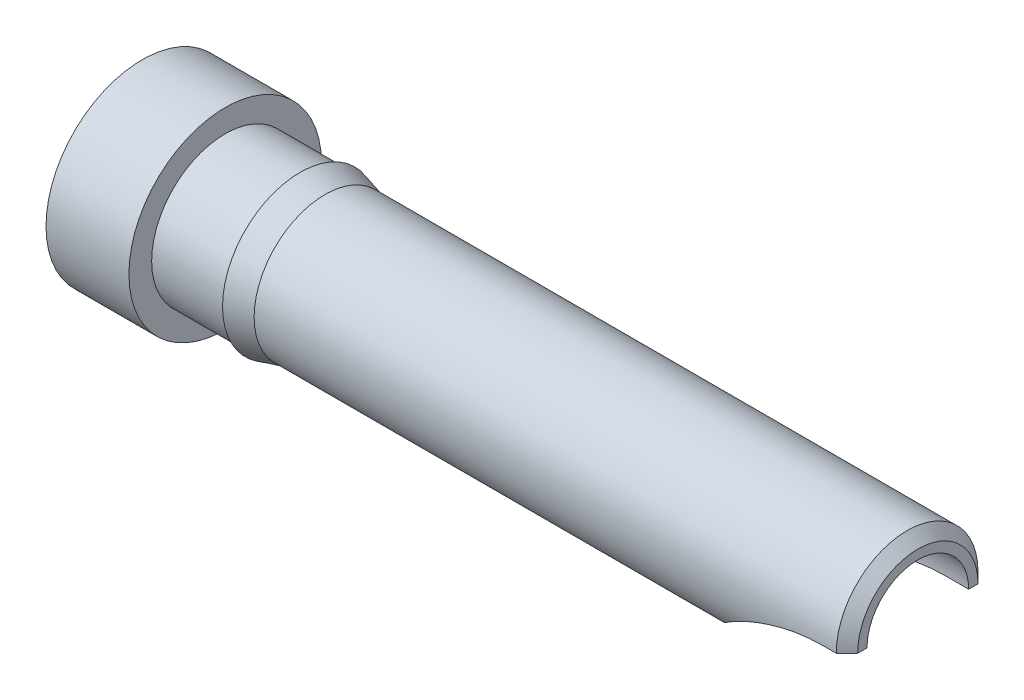
SolidWorks part; units mm, degrees
material "Brass Alloy 385"
ref_plane "Front Plane" through (0, 0, 0) normal (0, 0, 1) x (1, 0, 0)
ref_plane "Top Plane" through (0, 0, 0) normal (0, 1, 0) x (1, 0, 0)
ref_plane "Right Plane" through (0, 0, 0) normal (1, 0, 0) x (0, 0, -1)
sketch "Sketch1" plane through (0, 0, 0) normal (0, 0, 1) x (1, 0, 0)
  line L0 (7.2644, 0.6731) -> (7.366, 0.5715)
  line L1 (7.366, 0) -> (7.366, 0.5715)
  line L2 (1.7356, 0.6731) -> (7.2644, 0.6731)
  line L3 (1.4986, 0.7366) -> (1.7356, 0.6731)
  line L4 (1.4986, 0.6985) -> (1.4986, 0.7366)
  line L5 (0.7874, 0.6985) -> (1.4986, 0.6985)
  line L6 (0.7874, 0.9144) -> (0.7874, 0.6985)
  line L7 (0, 0.9144) -> (0.7874, 0.9144)
  line L8 (0, 0) -> (0, 0.9144)
  line L9 (0, 0) -> (7.366, 0)
  line L11 (0, 0) -> (7.366, 0) construction
  dimension "D4" = 0.6731
  dimension "D5" = 45
  dimension "D9" = 0.1016
revolve "RevolutionAngle1" add sketch "Sketch1" angle 360 about L11
hole_wizard "Hole1" positions "3DSketch1" profile "Sketch4" legacy
sketch3d "3DSketch1"
  line L0 (7.2644, 0, 0) -> (1.7356, 0, 0) construction
  point P0 (7.366, 0, 0)
sketch "Sketch4" plane through (7.366, 0, 0) normal (0, 1, 0) x (0, 0, -1)
  line L0 (0, 0) -> (0, 2.576)
  line L1 (0, 2.576) -> (0.4826, 2.286)
  line L2 (0.4826, 2.286) -> (0.4826, 0)
  line L4 (0.4826, 0) -> (0, 0)
  line L6 (0, 2.576) -> (-0.4826, 2.286) construction
  line L7 (0, -4.2442) -> (0, 117.3081) construction
  dimension "Diameter" = 0.9652
  dimension "Depth" = 2.286
  dimension "Drill Angle" = 118
sketch "Sketch6" plane through (0, 0, 0) normal (0, 0, 1) x (1, 0, 0)
  line L0 (5.842, -0.6731) -> (7.366, -0.6731)
  line L1 (7.366, 0) -> (7.366, -0.6731)
  line L2 (7.366, 0) -> (7.1463, 0)
  line L4 (7.366, -0.5715) -> (7.366, 0.5715) construction
  arc A0 (7.1463, 0) -> (5.842, -0.6731) centre (7.1463, -1.6002) ccw
  dimension "D1" = 0.6731
  dimension "D2" = 1.524
  dimension "D3" = 1.6002
extrude "Extrude1" cut sketch "Sketch6" against normal blind 0.6731 and the other way blind 0.6731
